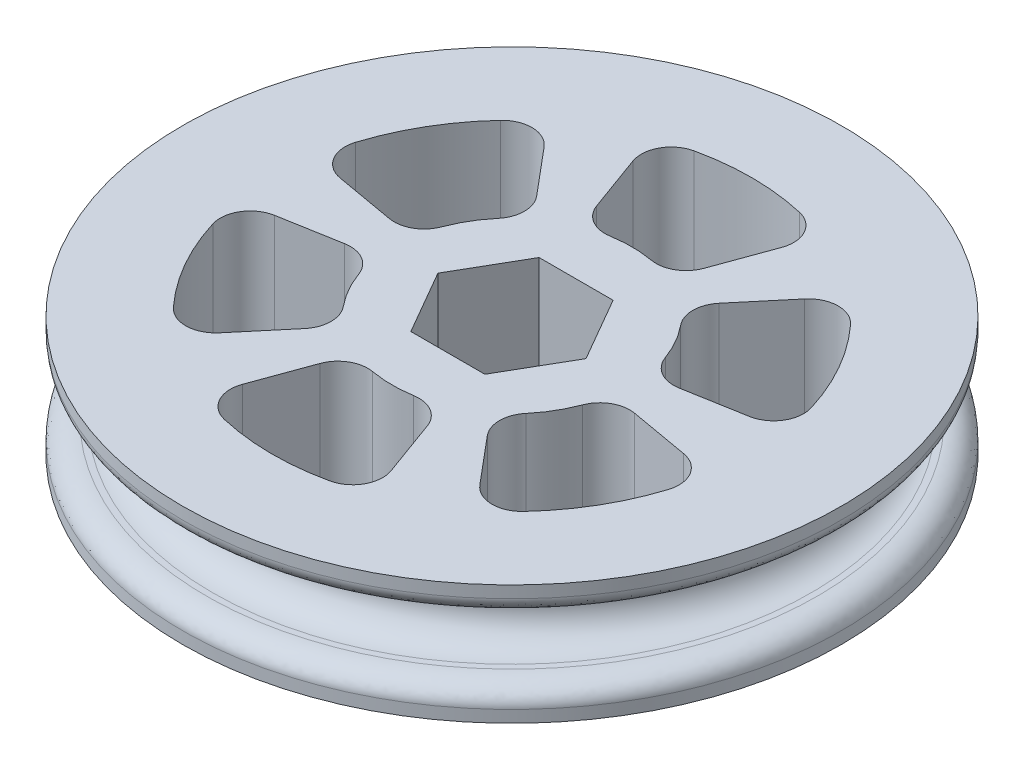
SolidWorks part; units mm, degrees
ref_plane "Front" through (0, 0, 0) normal (0, 0, 1) x (1, 0, 0)
ref_plane "Top" through (0, 0, 0) normal (0, 1, 0) x (1, 0, 0)
ref_plane "Right" through (0, 0, 0) normal (1, 0, 0) x (0, 0, -1)
sketch "Sketch1" plane through (0, 0, 0) normal (0, 1, 0) x (1, 0, 0)
  line L1 (7.8456, 0) -> (3.9228, 6.7945)
  line L2 (3.9228, 6.7945) -> (-3.9228, 6.7945)
  line L3 (-3.9228, 6.7945) -> (-7.8456, 0)
  line L4 (-7.8456, 0) -> (-3.9228, -6.7945)
  line L5 (-3.9228, -6.7945) -> (3.9228, -6.7945)
  line L6 (3.9228, -6.7945) -> (7.8456, 0)
  circle A0 centre (0, 0) radius 6.7945 construction
  circle A1 centre (0, 0) radius 34.925
  dimension "D1" = 69.85
extrude "Boss-Extrude1" add sketch "Sketch1" along normal blind 12.7
ref_plane "Mid_Plane" through (0, 6.35, 0) normal (0, -1, 0) x (-1, 0, 0)
sketch "Sketch4" plane through (-6.35, 6.35, 0) normal (0, 0, -1) x (0, 1, 0)
  line L0 (-6.35, 6.35) -> (-6.35, 41.275) construction
  line L1 (-6.35, 41.275) -> (0, 41.275) construction
  line L2 (0, 47.4649) -> (0, 38.1) construction
  line L3 (6.35, 41.275) -> (-6.35, 41.275) construction
  line L4 (0, 41.275) -> (6.35, 41.275) construction
  line L5 (-6.35, 41.275) -> (-6.35, -28.575) construction
  line L6 (3.175, 47.4649) -> (3.175, 38.1)
  line L7 (-3.175, 47.4649) -> (-3.175, 38.1)
  circle A1 centre (0, 41.275) radius 3.175 construction
  arc A2 (3.175, 47.4649) -> (-3.175, 47.4649) centre (0, 47.4649) ccw
  arc A3 (-3.175, 38.1) -> (3.175, 38.1) centre (0, 38.1) ccw
  point P13 (0, 42.7825)
  point P18 (0, 38.1)
  point P19 (0, 39.9064)
  dimension "D3" = 6.35
  dimension "D1" = 3.175
ref_axis "Axis1" through (0, 12.7, 0) along (0, -1, 0)
revolve "Cut-Revolve1" cut sketch "Sketch4" angle 360 about axis through (0, 12.7, 0) along (0, -1, 0)
sketch "Sketch5" plane through (0, 0, 0) normal (0, -1, 0) x (1, 0, 0)
  line L0 (5.6053, 14.5711) -> (7.8033, 20.6102)
  line L1 (-5.8088, 14.5356) -> (-8.0033, 20.5648)
  line L2 (0, 0) -> (0, 25.4) construction
  line L3 (15.4216, 2.4313) -> (21.7506, 3.5472)
  line L4 (9.6838, 12.2984) -> (13.808, 17.2134)
  line L5 (9.8163, -12.1398) -> (13.9473, -17.0629)
  line L6 (15.4927, -2.2372) -> (21.8113, -3.3514)
  line L7 (-5.6053, -14.5711) -> (-7.8033, -20.6102)
  line L8 (5.8088, -14.5356) -> (8.0033, -20.5648)
  line L9 (-15.4216, -2.4313) -> (-21.7506, -3.5472)
  line L10 (-9.6838, -12.2984) -> (-13.808, -17.2134)
  line L11 (-9.8163, 12.1398) -> (-13.9473, 17.0629)
  line L12 (-15.4927, 2.2372) -> (-21.8113, 3.3514)
  arc A0 (5.5083, 24.7955) -> (-5.7369, 24.7437) centre (0, 0) ccw
  arc A1 (2.0974, 12.5256) -> (-2.2603, 12.4972) centre (0, 0) ccw
  arc A2 (-2.2603, 12.4972) -> (-5.8088, 14.5356) centre (-2.8253, 15.6216) cw
  arc A3 (2.0974, 12.5256) -> (5.6053, 14.5711) centre (2.6217, 15.657) ccw
  arc A4 (7.8033, 20.6102) -> (5.5083, 24.7955) centre (4.8198, 21.6961) ccw
  arc A5 (-8.0033, 20.5648) -> (-5.7369, 24.7437) centre (-5.0197, 21.6507) cw
  arc A6 (24.2277, 7.6274) -> (18.5602, 17.3401) centre (0, 0) ccw
  arc A7 (11.8962, 4.4464) -> (9.6928, 8.2061) centre (0, 0) ccw
  arc A8 (9.6928, 8.2061) -> (9.6838, 12.2984) centre (12.116, 10.2576) cw
  arc A9 (11.8962, 4.4464) -> (15.4216, 2.4313) centre (14.8702, 5.558) ccw
  arc A10 (21.7506, 3.5472) -> (24.2277, 7.6274) centre (21.1993, 6.674) ccw
  arc A11 (13.808, 17.2134) -> (18.5602, 17.3401) centre (16.2402, 15.1726) cw
  arc A12 (18.7194, -17.1681) -> (24.2971, -7.4036) centre (0, 0) ccw
  arc A13 (9.7988, -8.0792) -> (11.9531, -4.2912) centre (0, 0) ccw
  arc A14 (11.9531, -4.2912) -> (15.4927, -2.2372) centre (14.9413, -5.364) cw
  arc A15 (9.7988, -8.0792) -> (9.8163, -12.1398) centre (12.2485, -10.099) ccw
  arc A16 (13.9473, -17.0629) -> (18.7194, -17.1681) centre (16.3795, -15.0221) ccw
  arc A17 (21.8113, -3.3514) -> (24.2971, -7.4036) centre (21.2599, -6.4781) cw
  arc A18 (-5.5083, -24.7955) -> (5.7369, -24.7437) centre (0, 0) ccw
  arc A19 (-2.0974, -12.5256) -> (2.2603, -12.4972) centre (0, 0) ccw
  arc A20 (2.2603, -12.4972) -> (5.8088, -14.5356) centre (2.8253, -15.6216) cw
  arc A21 (-2.0974, -12.5256) -> (-5.6053, -14.5711) centre (-2.6217, -15.657) ccw
  arc A22 (-7.8033, -20.6102) -> (-5.5083, -24.7955) centre (-4.8198, -21.6961) ccw
  arc A23 (8.0033, -20.5648) -> (5.7369, -24.7437) centre (5.0197, -21.6507) cw
  arc A24 (-24.2277, -7.6274) -> (-18.5602, -17.3401) centre (0, 0) ccw
  arc A25 (-11.8962, -4.4464) -> (-9.6928, -8.2061) centre (0, 0) ccw
  arc A26 (-9.6928, -8.2061) -> (-9.6838, -12.2984) centre (-12.116, -10.2576) cw
  arc A27 (-11.8962, -4.4464) -> (-15.4216, -2.4313) centre (-14.8702, -5.558) ccw
  arc A28 (-21.7506, -3.5472) -> (-24.2277, -7.6274) centre (-21.1993, -6.674) ccw
  arc A29 (-13.808, -17.2134) -> (-18.5602, -17.3401) centre (-16.2402, -15.1726) cw
  arc A30 (-18.7194, 17.1681) -> (-24.2971, 7.4036) centre (0, 0) ccw
  arc A31 (-9.7988, 8.0792) -> (-11.9531, 4.2912) centre (0, 0) ccw
  arc A32 (-11.9531, 4.2912) -> (-15.4927, 2.2372) centre (-14.9413, 5.364) cw
  arc A33 (-9.7988, 8.0792) -> (-9.8163, 12.1398) centre (-12.2485, 10.099) ccw
  arc A34 (-13.9473, 17.0629) -> (-18.7194, 17.1681) centre (-16.3795, 15.0221) ccw
  arc A35 (-21.8113, 3.3514) -> (-24.2971, 7.4036) centre (-21.2599, 6.4781) cw
  point P15 (0, 0)
  point P16 (0, 30.1625)
  point P77 (0, 0)
  dimension "D1" = 50.8
  dimension "D2" = 25.4
  dimension "D5" = 3.175
  dimension "D3" = 20
  dimension "D4" = 20
  dimension "D6" = 6
extrude "Cut-Extrude1" cut sketch "Sketch5" against normal through all
fillet "r" radius 2.54 2 edges at (0, 3.175, -34.925) (0, 9.525, 34.925) second distance 1.905 first distance on face at (0, 3.175, 31.75) first distance on face at (0, 9.525, 31.75)
